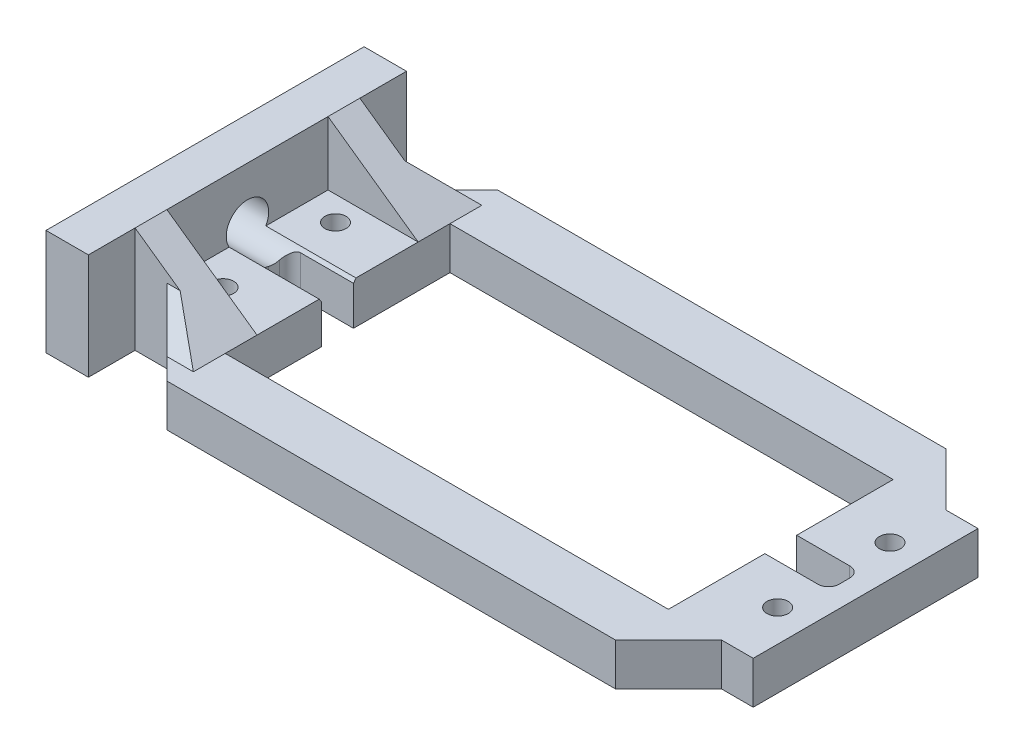
SolidWorks part; units mm, degrees
ref_plane "Front Plane" through (0, 0, 0) normal (0, 0, 1) x (1, 0, 0)
ref_plane "Top Plane" through (0, 0, 0) normal (0, 1, 0) x (1, 0, 0)
ref_plane "Right Plane" through (0, 0, 0) normal (1, 0, 0) x (0, 0, -1)
sketch "Sketch1" plane through (0, 0, 0) normal (0, 1, 0) x (1, 0, 0)
  line L0 (-29.4, 0) -> (-20.9, 0) construction
  line L1 (20.9, -10.6) -> (-20.9, -10.6)
  line L2 (20.9, -10.6) -> (20.9, -1.5)
  line L3 (20.9, 10.6) -> (-20.9, 10.6)
  line L4 (-20.9, -10.6) -> (-20.9, 10.6)
  line L5 (20.9, -10.6) -> (-20.9, 10.6) construction
  line L6 (20.9, 10.6) -> (-20.9, -10.6) construction
  line L7 (20.9, 15.6) -> (-21.4, 15.6)
  line L8 (20.9, 1.5) -> (20.9, 10.6)
  line L9 (20.9, -15.6) -> (-21.4, -15.6)
  line L10 (-26.4, 10.6) -> (-21.4, 15.6)
  line L11 (-0.25, 15.6) -> (-0.25, -15.6) construction
  line L12 (-25.9, -15.6) -> (-25.9, 15.6) construction
  line L13 (25.9, 15.6) -> (-25.9, 15.6) construction
  line L14 (25.9, 0) -> (-25.9, 0) construction
  line L15 (25.9, 10.6) -> (20.9, 15.6)
  line L16 (25.9, -10.6) -> (20.9, -15.6)
  line L17 (-26.4, -10.6) -> (-21.4, -15.6)
  line L18 (28.9, 0) -> (20.4, 0) construction
  line L19 (25.9, -15.6) -> (-25.9, -15.6) construction
  line L20 (25.9, -15.6) -> (25.9, 15.6) construction
  line L21 (-26.4, 10.6) -> (-29.4, 10.6)
  line L22 (-26.4, 10.6) -> (-26.4, -10.6)
  line L23 (-26.4, -10.6) -> (-29.4, -10.6)
  line L24 (-29.4, 10.6) -> (-29.4, -10.6)
  line L25 (25.9, -10.6) -> (28.9, -10.6)
  line L26 (28.9, 10.6) -> (28.9, -10.6)
  line L27 (25.9, 10.6) -> (28.9, 10.6)
  line L28 (-26.9, -1.5) -> (-20.9, -1.5)
  line L29 (-26.9, -1.5) -> (-26.9, 1.5)
  line L30 (-26.9, 1.5) -> (-20.9, 1.5)
  line L31 (-20.9, -1.5) -> (-20.9, 1.5)
  line L32 (-26.9, -1.5) -> (-20.9, 1.5) construction
  line L33 (-26.9, 1.5) -> (-20.9, -1.5) construction
  line L34 (26.9, -1.5) -> (20.9, -1.5)
  line L35 (26.9, -1.5) -> (26.9, 1.5)
  line L36 (26.9, 1.5) -> (20.9, 1.5)
  line L38 (26.9, -1.5) -> (20.9, 1.5) construction
  line L39 (26.9, 1.5) -> (20.9, -1.5) construction
  line L40 (20.9, -10.6) -> (20.9, 10.6) construction
  circle A0 centre (-26.4, 5.3) radius 1
  circle A1 centre (-26.4, -5.3) radius 1
  circle A2 centre (25.9, -5.3) radius 1
  circle A3 centre (25.9, 5.3) radius 1
  point P0 (0, 0)
  point P38 (-23.9, 0)
  point P43 (23.9, 0)
  dimension "D5" = 5.3
  dimension "D1" = 41.8
  dimension "D2" = 21.2
  dimension "D4" = 3
  dimension "D6" = 3
  dimension "D7" = 6
  dimension "D8" = 3
  dimension "D9" = 6
  dimension "D10" = 0
  dimension "D3" = 5
extrude "Boss-Extrude1" add sketch "Sketch1" along normal blind 4 contours L22 A1 L17 L9 L16 L25 L26 L27 L15 L7 L10 A0 L1 L4 L3 A2 A3 | L22 A1 A0 L21 L24 L23 region at (21.5349, 0, 6.05) region at (-27.9891, 0, 0)
fillet "Fillet1" radius 1 4 edges at (26.9, 2, 1.5) (26.9, 2, -1.5) (-26.9, 2, 1.5) (-26.9, 2, -1.5)
sketch "Sketch2" plane through (-29.4, 0, 0) normal (-1, 0, 0) x (0, 0, 1)
  line L0 (0, 0) -> (0, 10) construction
  line L1 (-10.6, 0) -> (10.6, 0) construction
  line L2 (15, 10) -> (-15, 10)
  line L3 (-15, 10) -> (-15, 0)
  line L4 (-10.6, 0) -> (-15.6, 0) construction
  line L5 (15, 10) -> (15, 0)
  line L6 (10.6, 0) -> (15.6, 0) construction
  line L7 (15, 0) -> (-15, 0)
  point P6 (0, 10)
  dimension "D1" = 10
  dimension "D2" = 30
extrude "Boss-Extrude2" add sketch "Sketch2" along normal blind 4
sketch "Sketch3" plane through (0, 4, 0) normal (0, 1, 0) x (1, 0, 0)
  line L0 (-20.9, -10.6) -> (-20.9, -1.5) construction
  line L1 (-20.9, -10.6) -> (-29.4, -10.6)
  line L2 (-20.9, -10.6) -> (-20.9, -7.6)
  line L3 (-20.9, -7.6) -> (-29.4, -7.6)
  line L4 (-29.4, -10.6) -> (-29.4, -7.6)
  line L5 (20.9, -10.6) -> (-20.9, -10.6) construction
  line L6 (-29.4, 10.6) -> (-29.4, -10.6) construction
  line L7 (-29.4, 0) -> (-15.8756, 0) construction
  line L8 (-29.4, 10.6) -> (-29.4, 7.6)
  line L9 (-20.9, 10.6) -> (-29.4, 10.6)
  line L10 (-20.9, 10.6) -> (-20.9, 7.6)
  line L11 (-20.9, 7.6) -> (-29.4, 7.6)
  dimension "D1" = 3
extrude "Boss-Extrude3" add sketch "Sketch3" along normal blind 6
sketch "Sketch4" plane through (0, 0, -10.6) normal (0, 0, -1) x (-1, 0, 0)
  line L0 (20.9, 4) -> (29.4, 10)
  line L1 (29.4, 10) -> (20.9, 10)
  line L2 (20.9, 10) -> (20.9, 4)
extrude "Cut-Extrude1" cut sketch "Sketch4" against normal through all
chamfer "Chamfer3" distance 3 angle 45 2 edges at (-23.65, 4, 10.6) (-23.65, 4, -10.6)
sketch "Sketch5" plane through (-33.4, 0, 0) normal (-1, 0, 0) x (0, 0, 1)
  circle A0 centre (0, 5) radius 2
  dimension "D1" = 5
  dimension "D2" = 4
extrude "Cut-Extrude2" cut sketch "Sketch5" against normal up to next
